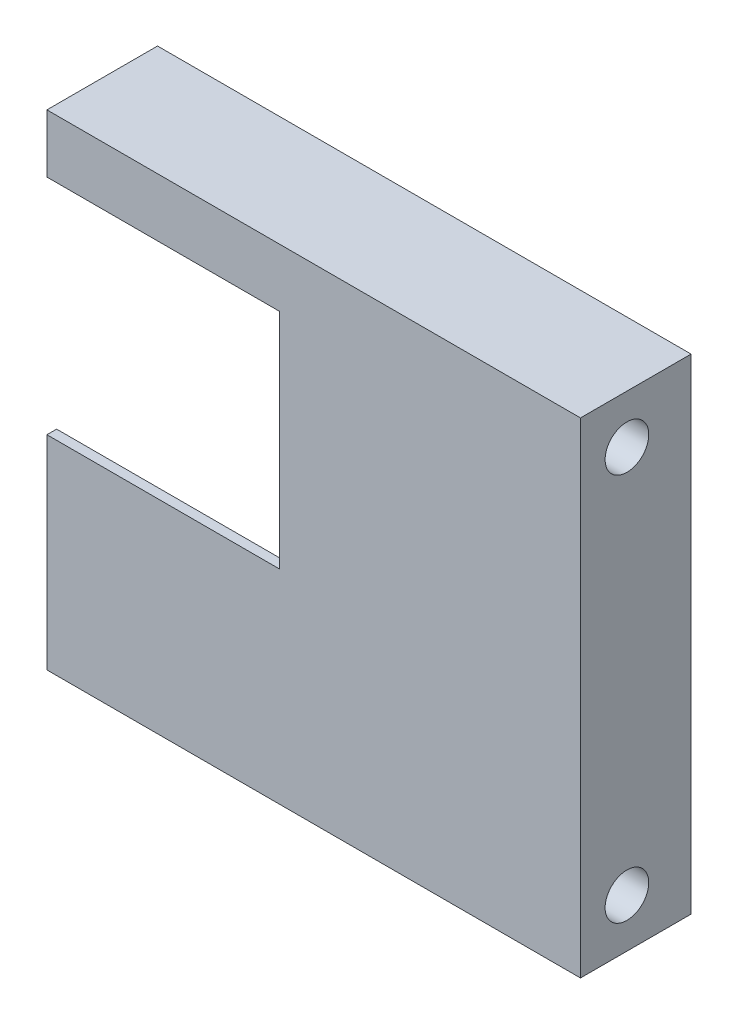
SolidWorks part; units mm, degrees
ref_plane "Front Plane" through (0, 0, 0) normal (1, 0, 0) x (0, 1, 0)
ref_plane "Top Plane" through (0, 0, 0) normal (0, 0, 1) x (0, 1, 0)
ref_plane "Right Plane" through (0, 0, 0) normal (0, 1, 0) x (-1, 0, 0)
sketch "Sketch1" plane through (0, 0, 0) normal (0, 0, 1) x (0, 1, 0)
  line L0 (-4, 25.3) -> (-4, 1.3)
  line L1 (-25, 25.3) -> (-4, 25.3)
  line L2 (-25, 25.3) -> (-25, -25.3)
  line L3 (-25, -25.3) -> (25, -25.3)
  line L4 (25, 25.3) -> (25, -25.3)
  line L5 (-25, 25.3) -> (25, -25.3) construction
  line L6 (-25, -25.3) -> (25, 25.3) construction
  line L7 (-4, 1.3) -> (19, 1.3)
  line L8 (19, 1.3) -> (19, 25.3)
  line L9 (19, 25.3) -> (25, 25.3)
  point P0 (0, 0)
  dimension "D1" = 50
  dimension "D2" = 50.6
  dimension "D3" = 24
  dimension "D4" = 23
extrude "Boss-Extrude1" add sketch "Sketch1" along normal blind 1
sketch "Sketch2" plane through (25.3, 0, 0) normal (1, 0, 0) x (0, 1, 0)
  line L1 (25, 1) -> (-25, 1)
  line L2 (25, 1) -> (25, -10.4)
  line L3 (25, -10.4) -> (-25, -10.4)
  line L4 (-25, 1) -> (-25, -10.4)
  dimension "D1" = 11.4
extrude "Boss-Extrude2" add sketch "Sketch2" along normal blind 4.4
sketch "Sketch3" plane through (29.7, 0, 0) normal (1, 0, 0) x (0, 1, 0)
  line L0 (-20, -3.7871) -> (20, -3.7871) construction
  line L1 (-25, 1) -> (-25, -10.4) construction
  circle A0 centre (-20, -3.7871) radius 2.25
  circle A1 centre (20, -3.7871) radius 2.25
  dimension "D1" = 4.5
  dimension "D2" = 4.5
  dimension "D3" = 40
  dimension "D4" = 5
extrude "Cut-Extrude1" cut sketch "Sketch3" against normal blind 4.4
sketch "Sketch4" plane through (0, 0, 0) normal (0, 0, -1) x (1, 0, 0)
  line L0 (-25.3, -19.5) -> (-25.3, -25)
  line L1 (-25.3, 19.5) -> (25.3, 19.5)
  line L3 (-25.3, -19.5) -> (25.3, -19.5)
  line L7 (-25.3, 25) -> (25.3, 25)
  line L8 (-25.3, 25) -> (-25.3, 19.5)
  line L9 (-25.3, -25) -> (25.3, -25)
  line L10 (25.3, 25) -> (25.3, 19.5)
  line L11 (-25.3, 25) -> (-19.734, 19.5) construction
  line L12 (-25.3, -25) -> (-19.734, -19.5) construction
  line L13 (19.734, 19.5) -> (25.3, 25) construction
  line L14 (19.734, -19.5) -> (25.3, -25) construction
  line L15 (25.3, -19.5) -> (25.3, -25)
  point P0 (0, 0)
  point P6 (0, 0)
  dimension "D1" = 50.6
  dimension "D2" = 39
  dimension "D3" = 5.5
  dimension "D4" = 5.5
extrude "Boss-Extrude3" add sketch "Sketch4" along normal blind 6.4
sketch "Sketch5" plane through (0, 0, -6.4) normal (0, 0, -1) x (1, 0, 0)
  line L0 (-25.3, 20.5) -> (-25.3, 25)
  line L5 (25.3, -25) -> (-25.3, -25)
  line L6 (25.3, -20.5) -> (-25.3, -20.5)
  line L13 (25.3, 20.5) -> (-25.3, 20.5)
  line L18 (25.3, -25) -> (25.3, -20.5)
  line L19 (25.3, 25) -> (-25.3, 25)
  line L20 (-25.3, -25) -> (-25.3, -20.5)
  line L21 (25.3, -25) -> (20.746, -20.5) construction
  line L22 (25.3, 25) -> (20.746, 20.5) construction
  line L23 (-20.746, -20.5) -> (-25.3, -25) construction
  line L24 (-20.746, 20.5) -> (-25.3, 25) construction
  line L25 (25.3, 20.5) -> (25.3, 25)
  point P0 (0, 0)
  point P5 (0, 0)
  dimension "D1" = 41
  dimension "D2" = 50.6
extrude "Boss-Extrude4" add sketch "Sketch5" along normal blind 2
sketch "Sketch6" plane through (0, 0, -8.4) normal (0, 0, -1) x (1, 0, 0)
  line L0 (-25.3, -19.5) -> (-25.3, -25)
  line L5 (19.734, -19.5) -> (25.3, -25) construction
  line L23 (25.3, 19.5) -> (-25.3, 19.5)
  line L37 (25.3, -19.5) -> (-25.3, -19.5)
  line L41 (-25.3, 25) -> (25.3, 25)
  line L42 (-25.3, 25) -> (-25.3, 19.5)
  line L43 (-25.3, -25) -> (25.3, -25)
  line L44 (25.3, 25) -> (25.3, 19.5)
  line L46 (-25.3, -25) -> (-19.734, -19.5) construction
  line L47 (25.3, -19.5) -> (25.3, -25)
  point P0 (0, 0)
  point P5 (-7.2876, 5.6169)
  point P6 (0, 0)
  dimension "D1" = 50.6
  dimension "D2" = 39
  dimension "D3" = 50.6
  dimension "D4" = 50
extrude "Boss-Extrude5" add sketch "Sketch6" along normal blind 2
